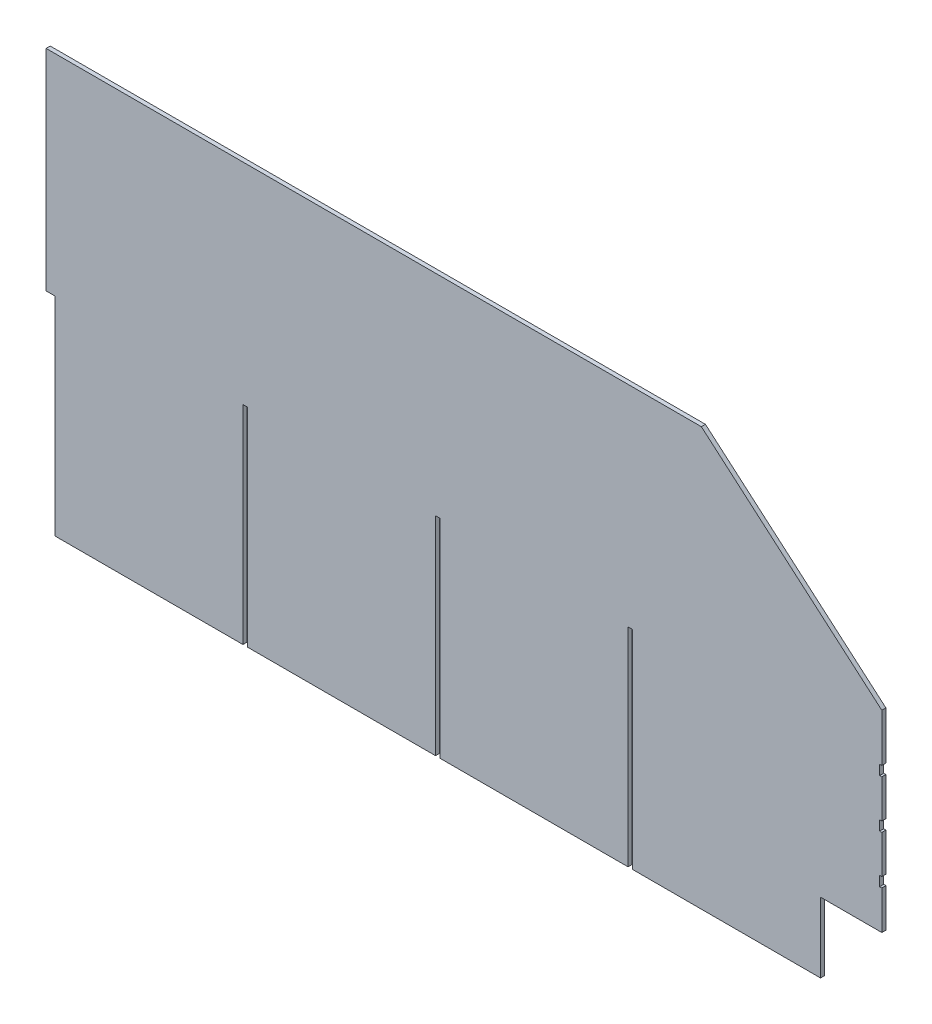
SolidWorks part; units mm, degrees
material "Pine"
ref_plane "Front Plane" through (0, 0, 0) normal (0, 0, 1) x (1, 0, 0)
ref_plane "Top Plane" through (0, 0, 0) normal (0, 1, 0) x (1, 0, 0)
ref_plane "Right Plane" through (0, 0, 0) normal (1, 0, 0) x (0, 0, -1)
sketch "Sketch1" plane through (0, 0, 0) normal (0, 0, 1) x (1, 0, 0)
  line L0 (-914.9045, -420.6391) -> (-368.8045, -420.6391) construction
  line L1 (-940.3045, 792.2109) -> (961.6475, 792.2109)
  line L2 (-940.3045, 792.2109) -> (-940.3045, 182.6109)
  line L3 (-914.9045, -420.6391) -> (-368.8045, -420.6391)
  line L4 (1485.3955, 341.3609) -> (1485.3955, -217.4391)
  line L7 (-940.3045, 182.6109) -> (-914.9045, 182.6109)
  line L8 (-914.9045, -420.6391) -> (-914.9045, 182.6109)
  line L9 (-356.1045, -420.6391) -> (189.9955, -420.6391) construction
  line L11 (-368.8045, -420.6391) -> (-368.8045, 182.6109)
  line L12 (-368.8045, 182.6109) -> (-356.1045, 182.6109)
  line L13 (-356.1045, -420.6391) -> (-356.1045, 182.6109)
  line L14 (202.6955, -420.6391) -> (748.7955, -420.6391) construction
  line L16 (189.9955, -420.6391) -> (189.9955, 182.6109)
  line L17 (189.9955, 182.6109) -> (202.6955, 182.6109)
  line L18 (202.6955, -420.6391) -> (202.6955, 182.6109)
  line L19 (961.6475, 792.2109) -> (1485.3955, 341.3609)
  line L21 (748.7955, -420.6391) -> (748.7955, 182.6109)
  line L22 (748.7955, 182.6109) -> (761.4955, 182.6109)
  line L23 (761.4955, -420.6391) -> (761.4955, 182.6109)
  line L24 (1485.3955, 341.3609) -> (1485.3955, -217.4391) construction
  line L25 (-356.1045, -420.6391) -> (189.9955, -420.6391)
  line L26 (1307.5955, -420.6391) -> (1307.5955, -217.4391)
  line L27 (1307.5955, -217.4391) -> (1485.3955, -217.4391)
  line L28 (202.6955, -420.6391) -> (748.7955, -420.6391)
  line L29 (761.4955, -420.6391) -> (1307.5955, -420.6391)
  dimension "D2" = 558.8
  dimension "D3" = 25.4
  dimension "D4" = 603.25
  dimension "D5" = 546.1
  dimension "D6" = 12.7
  dimension "D7" = 546.1
  dimension "D8" = 12.7
  dimension "D9" = 546.1
  dimension "D10" = 12.7
  dimension "D11" = 1212.85
  dimension "D12" = 203.2
  dimension "D13" = 1901.952
  dimension "D14" = 177.8
  dimension "D15" = 723.9
  dimension "D16" = 2425.7
extrude "Boss-Extrude1" add sketch "Sketch1" along normal blind 11.9062
sketch "Sketch2" plane through (0, 0, 11.9062) normal (0, 0, 1) x (1, 0, 0)
  line L0 (1485.3955, -217.4391) -> (1485.3955, 341.3609) construction
  line L1 (1485.3955, -105.4886) -> (1479.0455, -105.4886)
  line L2 (1485.3955, -105.4886) -> (1485.3955, -76.9136)
  line L3 (1485.3955, -76.9136) -> (1479.0455, -76.9136)
  line L4 (1479.0455, -105.4886) -> (1479.0455, -76.9136)
  line L5 (1307.5955, -217.4391) -> (1485.3955, -217.4391) construction
  line L6 (1485.3955, 34.2114) -> (1479.0455, 34.2114)
  line L7 (1485.3955, 34.2114) -> (1485.3955, 62.7864)
  line L8 (1485.3955, 62.7864) -> (1479.0455, 62.7864)
  line L9 (1479.0455, 34.2114) -> (1479.0455, 62.7864)
  line L10 (1485.3955, 173.9114) -> (1479.0455, 173.9114)
  line L11 (1485.3955, 173.9114) -> (1485.3955, 202.4864)
  line L12 (1485.3955, 202.4864) -> (1479.0455, 202.4864)
  line L13 (1479.0455, 173.9114) -> (1479.0455, 202.4864)
  point P14 (1479.0455, -91.2011)
  point P17 (1479.0455, 48.4989)
  point P18 (1479.0455, 188.1989)
  dimension "D1" = 6.35
  dimension "D2" = 28.575
  dimension "D3" = 126.238
  dimension "D4" = 265.938
  dimension "D5" = 405.638
extrude "Cut-Extrude1" cut sketch "Sketch2" against normal through all
